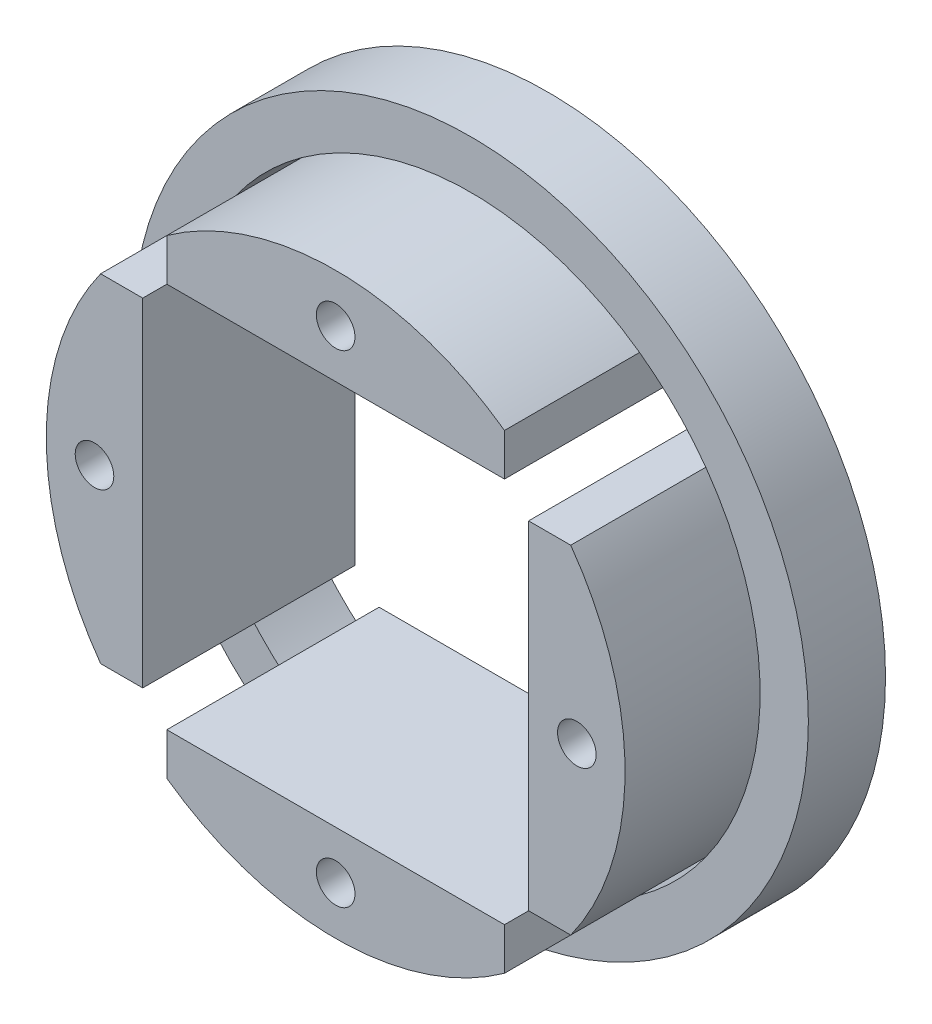
SolidWorks part; units mm, degrees
ref_plane "前视基准面" through (0, 0, 0) normal (0, 0, 1) x (1, 0, 0)
ref_plane "上视基准面" through (0, 0, 0) normal (0, 1, 0) x (1, 0, 0)
ref_plane "右视基准面" through (0, 0, 0) normal (1, 0, 0) x (0, 0, -1)
sketch "草图1" plane through (0, 0, 0) normal (0, 0, 1) x (1, 0, 0)
  line L0 (-8.75, 10) -> (8.75, 10)
  line L1 (-8.75, 10) -> (-8.75, 12.1835)
  line L2 (8.75, 10) -> (8.75, 12.1835)
  line L3 (10, 8.75) -> (10, -8.75)
  line L4 (10, 8.75) -> (12.1835, 8.75)
  line L5 (10, -8.75) -> (12.1835, -8.75)
  line L6 (8.75, -10) -> (-8.75, -10)
  line L7 (8.75, -10) -> (8.75, -12.1835)
  line L8 (-8.75, -10) -> (-8.75, -12.1835)
  line L9 (-10, -8.75) -> (-10, 8.75)
  line L10 (-10, -8.75) -> (-12.1835, -8.75)
  line L11 (-10, 8.75) -> (-12.1835, 8.75)
  circle A0 centre (0, 0) radius 15
  circle A1 centre (0, 12.5) radius 1
  circle A2 centre (12.5, 0) radius 1
  circle A3 centre (0, -12.5) radius 1
  circle A4 centre (-12.5, 0) radius 1
  circle A5 centre (0, 0) radius 17.5
  point P3 (0, 10)
  point P31 (0, 0)
  dimension "D1" = 30
  dimension "D3" = 2
  dimension "D7" = 35
  dimension "D2" = 12.5
  dimension "D4" = 17.5
  dimension "D5" = 10
  dimension "D6" = 4
extrude "凸台-拉伸1" add sketch "草图1" along normal blind 7 contours L11 A0 L10 L9 A4 | L2 A0 L1 L0 A1 | L5 A0 L4 L3 A2 | L8 A0 L7 L6 A3 region at (-8.568, 11.0917, 0) region at (-11.0917, 8.568, 0) region at (14.1053, 4.5403, 0) region at (-8.568, -11.0917, 0)
extrude "凸台-拉伸2" add sketch "草图1<3>" against normal blind 4 contours A5 A0 | L2 A0 L1 L0 A1 | L5 A0 L4 L3 A2 | L8 A0 L7 L6 A3 | L11 A0 L10 L9 A4 region at (-8.568, 11.0917, 0) region at (-11.0917, 8.568, 0) region at (14.1053, 4.5403, 0) region at (-8.568, -11.0917, 0) region at (-17.005, 0, 0)
sketch "草图1<3>" plane through (0, 0, 0) normal (0, 0, 1) x (1, 0, 0) same geometry as "草图1"
sketch "草图2" plane through (0, 0, -4) normal (0, 0, -1) x (-1, 0, 0)
  line L0 (10.5, -1.1547) -> (12.5, -2.3094)
  line L1 (1.1547, 10.5) -> (2.3094, 12.5)
  line L2 (2.3094, 12.5) -> (1.1547, 14.5)
  line L3 (1.1547, 14.5) -> (-1.1547, 14.5)
  line L4 (-1.1547, 14.5) -> (-2.3094, 12.5)
  line L5 (-2.3094, 12.5) -> (-1.1547, 10.5)
  line L6 (-1.1547, 10.5) -> (1.1547, 10.5)
  line L7 (12.5, -2.3094) -> (14.5, -1.1547)
  line L8 (14.5, -1.1547) -> (14.5, 1.1547)
  line L9 (14.5, 1.1547) -> (12.5, 2.3094)
  line L10 (12.5, 2.3094) -> (10.5, 1.1547)
  line L11 (10.5, 1.1547) -> (10.5, -1.1547)
  line L12 (-1.1547, -10.5) -> (-2.3094, -12.5)
  line L13 (-2.3094, -12.5) -> (-1.1547, -14.5)
  line L14 (-1.1547, -14.5) -> (1.1547, -14.5)
  line L15 (1.1547, -14.5) -> (2.3094, -12.5)
  line L16 (2.3094, -12.5) -> (1.1547, -10.5)
  line L17 (1.1547, -10.5) -> (-1.1547, -10.5)
  line L18 (-10.5, 1.1547) -> (-12.5, 2.3094)
  line L19 (-12.5, 2.3094) -> (-14.5, 1.1547)
  line L20 (-14.5, 1.1547) -> (-14.5, -1.1547)
  line L21 (-14.5, -1.1547) -> (-12.5, -2.3094)
  line L22 (-12.5, -2.3094) -> (-10.5, -1.1547)
  line L23 (-10.5, -1.1547) -> (-10.5, 1.1547)
  circle A0 centre (0, 12.5) radius 2 construction
  point P30 (0, 0)
  dimension "D1" = 4
  dimension "D2" = 4
extrude "切除-拉伸1" cut sketch "草图2" against normal blind 3
